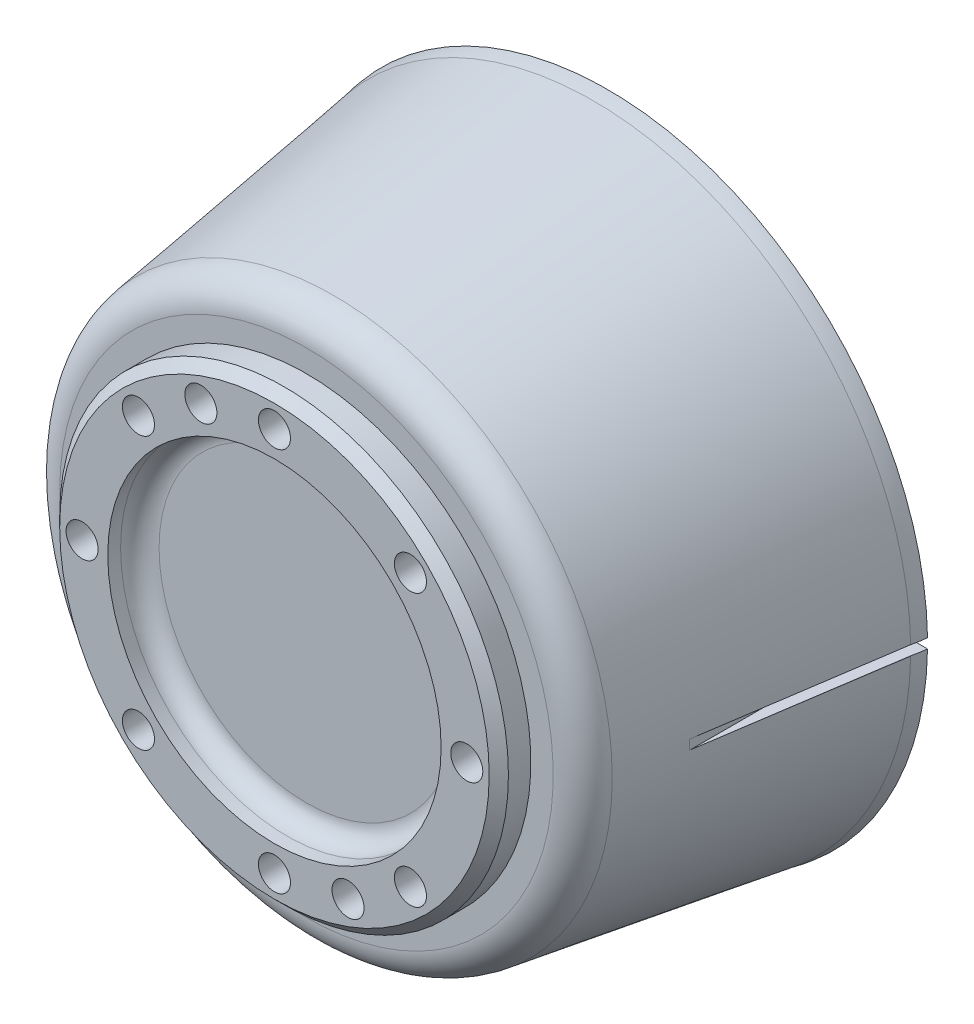
SolidWorks part; units mm, degrees
ref_plane "前基準面" through (0, 0, 0) normal (0, 0, 1) x (1, 0, 0)
ref_plane "上基準面" through (0, 0, 0) normal (0, 1, 0) x (1, 0, 0)
ref_plane "右基準面" through (0, 0, 0) normal (1, 0, 0) x (0, 0, -1)
sketch "草圖1" plane through (0, 0, 0) normal (0, 0, 1) x (1, 0, 0)
  line L0 (0.476, 0) -> (49.5, 0) construction
  line L1 (49.9944, -0.75) -> (49.9944, 0.75) construction
  line L2 (49.9944, -0.75) -> (45.0001, -0.75)
  line L4 (49.9944, 0.75) -> (45.0001, 0.75)
  line L5 (45.0001, -0.75) -> (45.0001, 0.75)
  line L6 (49.5, 0) -> (45.0001, 0.75) construction
  line L7 (49.5, 0) -> (45.0001, -0.75) construction
  arc A0 (49.9944, 0.75) -> (49.9944, -0.75) centre (0, 0) ccw
  dimension "D3" = 100
  dimension "D1" = 4.9943
  dimension "D2" = 1.5
extrude "填料-伸長1" add sketch "草圖1" along normal blind 2.25
ref_plane "平面1" through (0, 0, 47) normal (0, 0, 1) x (1, 0, 0)
sketch "草圖2" plane through (0, 0, 47) normal (0, 0, 1) x (1, 0, 0)
  line L0 (42.795, 0) -> (0, 0) construction
  circle A0 centre (0, 0) radius 42.795
  dimension "D1" = 85.59
sketch "草圖3" plane through (0, 0, 0) normal (0, 1, 0) x (1, 0, 0)
  line L0 (0, 0) -> (0, -47) construction
  line L3 (-54.9969, -47) -> (54.9969, -47) construction
  line L4 (-49.4943, 0) -> (-42.795, -47) construction
  line L5 (49.4943, 0) -> (0, 0)
  line L6 (0, 0) -> (0, -47)
  line L7 (0, -47) -> (42.795, -47)
  line L9 (49.4943, 0) -> (49.4943, -2.25)
  line L10 (49.4943, -2.25) -> (42.795, -47)
  dimension "D1" = 85.59
  dimension "D2" = 49.4943
revolve "旋轉1" add sketch "草圖3" angle 360 about L6
sketch "草圖12" plane through (0, 0, 0) normal (0, 0, -1) x (-1, 0, 0)
  line L1 (-53.9999, 0.75) -> (-45.0001, 0.75)
  line L2 (-53.9999, 0.75) -> (-53.9999, -0.75)
  line L3 (-53.9999, -0.75) -> (-45.0001, -0.75)
  line L4 (-45.0001, 0.75) -> (-45.0001, -0.75)
  line L5 (-53.9999, 0.75) -> (-45.0001, -0.75) construction
  line L6 (-53.9999, -0.75) -> (-45.0001, 0.75) construction
  point P0 (-49.5, 0)
extrude "除料-伸長1" cut sketch "草圖12" against normal up to surface (47 mm away) up to face at (-42.795, 0, 47)
fillet "圓角1" radius 20 1 edges at (-50, 0, 2.25)
fillet "圓角2" radius 5 1 edges at (-42.795, 0, 47)
sketch "草圖13" plane through (0, 0, 47) normal (0, 0, 1) x (1, 0, 0)
  circle A0 centre (0, 0) radius 35
  circle A1 centre (0, 0) radius 26
  dimension "D1" = 70
  dimension "D2" = 52
extrude "填料-伸長2" add sketch "草圖13" along normal blind 5
fillet "圓角4" radius 3 1 edges at (26, 0, 47)
chamfer "導角1" distance 1.5 angle 45 1 edges at (35, 0, 52)
sketch "草圖14" plane through (0, 0, 52) normal (0, 0, 1) x (1, 0, 0)
  line L0 (0, 0) -> (33.5, 0) construction
  line L1 (42.795, 0) -> (0, 0) construction
  line L2 (0, 0) -> (0, -33.5) construction
  circle A0 centre (0, 0) radius 33.5 construction
  point P10 (0, 0)
sketch "草圖15" plane through (0, 0, 52) normal (0, 0, 1) x (1, 0, 0)
  line L0 (42.795, 0) -> (0, 0) construction
  line L1 (0, 0) -> (0, -33.5) construction
  line L2 (21.2132, 21.2132) -> (0, 0) construction
  line L3 (0, 0) -> (0, 30) construction
  line L4 (0, 0) -> (-11.4805, 27.7164) construction
  line L5 (0, 0) -> (-21.2132, 21.2132) construction
  line L6 (0, 0) -> (-30, 0) construction
  line L7 (0, 0) -> (-21.2132, -21.2132) construction
  line L8 (0, 0) -> (11.4805, -27.7164) construction
  line L9 (0, 0) -> (21.2132, -21.2132) construction
  circle A0 centre (30, 0) radius 2.5
  circle A1 centre (0, -30) radius 2.5
  circle A2 centre (0, 30) radius 2.5
  circle A3 centre (-11.4805, 27.7164) radius 2.5
  circle A4 centre (-21.2132, 21.2132) radius 2.5
  circle A5 centre (21.2132, 21.2132) radius 2.5
  circle A6 centre (21.2132, -21.2132) radius 2.5
  circle A7 centre (11.4805, -27.7164) radius 2.5
  circle A9 centre (-30, 0) radius 2.5
  circle A10 centre (-21.2132, -21.2132) radius 2.5
  circle A12 centre (0, 0) radius 30 construction
  dimension "D1" = 5
  dimension "D3" = 22.5
  dimension "D8" = 60
  dimension "D2" = 45
  dimension "D4" = 45
  dimension "D5" = 45
  dimension "D6" = 22.5
  dimension "D7" = 45
extrude "除料-伸長2" cut sketch "草圖15" against normal up to surface (5 mm away) up to face at (-35, 0, 47)
ref_point "點1"
ref_point "點2"
ref_point "點3"
ref_point "點4"
